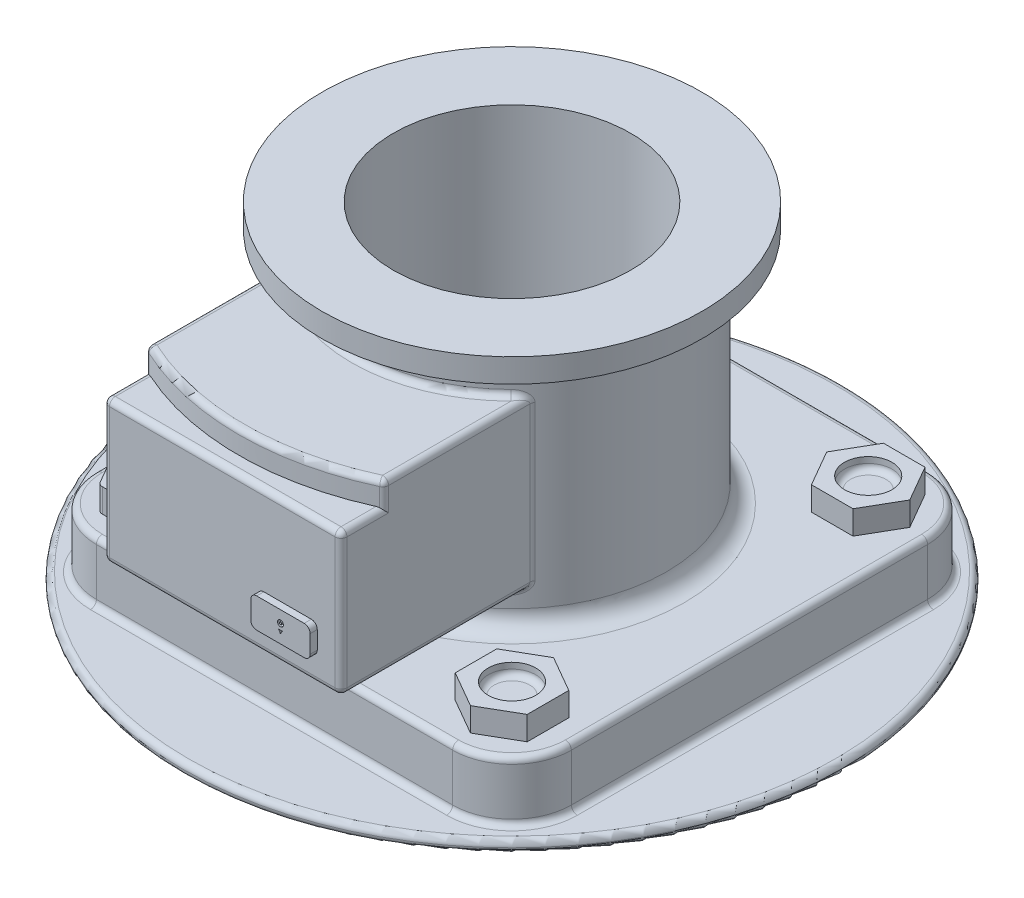
SolidWorks part; units mm, degrees
ref_plane "Front Plane" through (0, 0, 0) normal (0, 0, 1) x (1, 0, 0)
ref_plane "Top Plane" through (0, 0, 0) normal (0, 1, 0) x (1, 0, 0)
ref_plane "Right Plane" through (0, 0, 0) normal (1, 0, 0) x (0, 0, -1)
sketch "Sketch1" plane through (0, 0, 0) normal (0, 1, 0) x (1, 0, 0)
  circle A0 centre (0, 0) radius 277.5
  dimension "D1" = 555
extrude "Boss-Extrude1" add sketch "Sketch1" along normal blind 10
sketch "Sketch2" plane through (0, 10, 0) normal (0, 1, 0) x (1, 0, 0)
  line L1 (-200, -200) -> (200, -200)
  line L2 (-200, -200) -> (-200, 200)
  line L3 (-200, 200) -> (200, 200)
  line L4 (200, -200) -> (200, 200)
  line L5 (-200, -200) -> (200, 200) construction
  line L6 (-200, 200) -> (200, -200) construction
  point P0 (0, 0)
  dimension "D1" = 400
  dimension "D2" = 400
extrude "Boss-Extrude2" add sketch "Sketch2" along normal blind 50
fillet "Fillet1" radius 50 4 edges at (-200, 35, -200) (200, 35, -200) (200, 35, 200) (-200, 35, 200)
sketch "Sketch3" plane through (0, 60, 0) normal (0, 1, 0) x (1, 0, 0)
  circle A0 centre (0, 0) radius 130
  dimension "D1" = 260
extrude "Boss-Extrude3" add sketch "Sketch3" along normal blind 200
sketch "Sketch4" plane through (0, 260, 0) normal (0, 1, 0) x (1, 0, 0)
  circle A0 centre (0, 0) radius 160
  dimension "D1" = 320
extrude "Boss-Extrude4" add sketch "Sketch4" along normal blind 20
sketch "Sketch5" plane through (0, 0, 0) normal (0, 0, 1) x (1, 0, 0)
  line L0 (0, 160) -> (0, 0) construction
  line L1 (-150, 60) -> (150, 60) construction
  line L2 (-100, 90) -> (100, 90)
  line L3 (-100, 90) -> (-100, 230)
  line L4 (-100, 230) -> (100, 230)
  line L5 (100, 90) -> (100, 230)
  line L6 (-100, 90) -> (100, 230) construction
  line L7 (-100, 230) -> (100, 90) construction
  dimension "D1" = 140
  dimension "30" = 30
  dimension "D2" = 200
extrude "Boss-Extrude5" add sketch "Sketch5" along normal blind 244
sketch "Sketch6" plane through (0, 230, 0) normal (0, 1, 0) x (1, 0, 0)
  circle A0 centre (0, 0) radius 230
  dimension "D1" = 460
extrude "Cut-Extrude1" cut sketch "Sketch6" against normal blind 20 flip side to cut
sketch "Sketch7" plane through (0, 280, 0) normal (0, 1, 0) x (1, 0, 0)
  circle A0 centre (0, 0) radius 100
  circle A1 centre (0, 0) radius 160 construction
  dimension "D1" = 200
extrude "Cut-Extrude2" cut sketch "Sketch7" against normal blind 200
fillet "Fillet2" radius 5 17 edges at (0, 90, 130) (-100, 90, 163.5331) (-100, 160, 83.0662) (-100, 220, 207.1232) (-100, 210, 225.5616) (-100, 230, 145.0947) (0, 230, 130) (0, 230, 230) (0, 90, 244) (-100, 150, 244) (0, 210, 244) (100, 220, 207.1232) (100, 230, 145.0947) (100, 160, 83.0662) (100, 90, 163.5331) (100, 150, 244) (100, 210, 225.5616)
fillet "Fillet3" radius 15 1 edges at (0, 60, 130)
fillet "Fillet4" radius 5 18 edges at (185.3553, 60, -185.3553) (200, 60, 0) (185.3553, 60, 185.3553) (0, 60, 200) (-185.3553, 60, 185.3553) (-200, 60, 0) (-185.3553, 60, -185.3553) (0, 60, -200) (-185.3553, 10, 185.3553) (0, 10, 200) (185.3553, 10, 185.3553) (200, 10, 0) (185.3553, 10, -185.3553) (0, 10, -200) (-185.3553, 10, -185.3553) (-200, 10, 0) (0, 10, 277.5) (0, 0, 277.5)
sketch "Sketch8" plane through (0, 0, 244) normal (0, 0, 1) x (1, 0, 0)
  line L0 (-95, 95) -> (95, 95) construction
  line L1 (30, 110) -> (80, 110)
  line L2 (30, 110) -> (30, 135)
  line L3 (30, 135) -> (80, 135)
  line L4 (80, 110) -> (80, 135)
  line L5 (30, 110) -> (80, 135) construction
  line L6 (30, 135) -> (80, 110) construction
  line L7 (95, 95) -> (95, 205) construction
  point P0 (55, 122.5)
  dimension "D1" = 15
  dimension "D2" = 15
  dimension "D3" = 50
  dimension "D4" = 25
extrude "Boss-Extrude6" add sketch "Sketch8" along normal blind 6
fillet "Fillet5" radius 5 4 edges at (30, 135, 247) (30, 110, 247) (80, 110, 247) (80, 135, 247)
sketch "Sketch9" plane through (0, 0, 250) normal (0, 0, 1) x (1, 0, 0)
  line L0 (55, 135) -> (55, 125) construction
  line L1 (75, 135) -> (35, 135) construction
  circle A0 centre (55, 125) radius 1
  circle A1 centre (55, 125) radius 2.5
  circle A2 centre (55, 125) radius 5
  circle A3 centre (50, 116.3397) radius 5
  circle A4 centre (60, 116.3397) radius 5
  dimension "D1" = 10
  dimension "D2" = 2
  dimension "D3" = 5
  dimension "D4" = 10
extrude "Cut-Extrude3" cut sketch "Sketch9" against normal blind 10 contours A3 A4 A2 region at (55, 119.2265, 250)
extrude "Cut-Extrude4" cut sketch "Sketch9<3>" against normal blind 2 contours A1 A0 region at (52.5707, 125, 250)
sketch "Sketch9<3>" plane through (0, 0, 250) normal (0, 0, 1) x (1, 0, 0) same geometry as "Sketch9"
fillet "Fillet6" radius 1 1 edges at (57.5, 125, 248)
chamfer "Chamfer1" distance 0.1 angle 45 1 edges at (56, 125, 250)
sketch "Sketch11" plane through (0, 60, 0) normal (0, 1, 0) x (1, 0, 0)
  line L0 (195, -150) -> (195, 150) construction
  line L1 (150, -115) -> (119.6891, -132.5)
  line L2 (119.6891, -132.5) -> (119.6891, -167.5)
  line L3 (119.6891, -167.5) -> (150, -185)
  line L4 (150, -185) -> (180.3109, -167.5)
  line L5 (180.3109, -167.5) -> (180.3109, -132.5)
  line L6 (180.3109, -132.5) -> (150, -115)
  circle A0 centre (150, -150) radius 30.3109 construction
  dimension "D1" = 35
extrude "Boss-Extrude7" add sketch "Sketch11" along normal blind 20
sketch "Sketch12" plane through (0, 80, 0) normal (0, 1, 0) x (1, 0, 0)
  circle A0 centre (150, -150) radius 20
  dimension "D1" = 40
extrude "Cut-Extrude5" cut sketch "Sketch12" against normal blind 10
fillet "Fillet7" radius 5 1 edges at (150, 70, 170)
pattern_circular "CirPattern7" count 4 over 360 about axis through (0, 60, 0) along (0, -1, 0) of "Boss-Extrude7"
pattern_circular "CirPattern9" count 4 over 360 about axis through (0, 60, 0) along (0, -1, 0) of "Fillet7", "Cut-Extrude5"
fillet "Fillet8" radius 5 6 edges at (-115, 70, 150) (-132.5, 70, 119.6891) (-167.5, 70, 119.6891) (-132.5, 70, 180.3109) (-167.5, 70, 180.3109) (-185, 70, 150)
